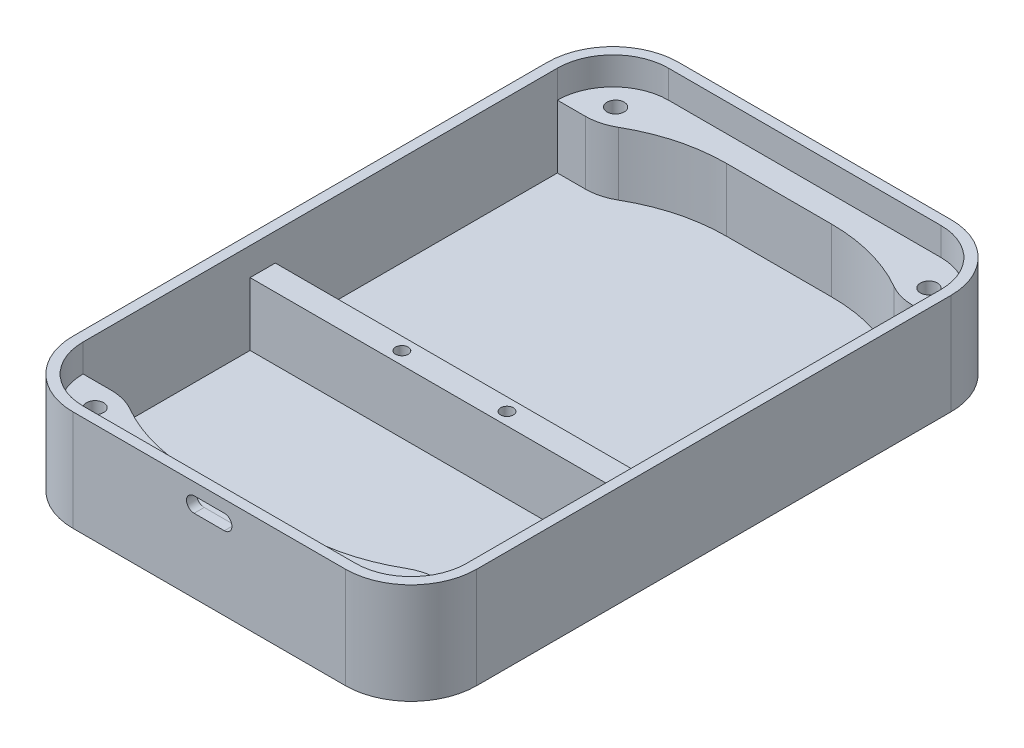
SolidWorks part; units mm, degrees
ref_plane "Alzado" through (0, 0, 0) normal (0, 0, 1) x (1, 0, 0)
ref_plane "Planta" through (0, 0, 0) normal (0, 1, 0) x (1, 0, 0)
ref_plane "Vista lateral" through (0, 0, 0) normal (1, 0, 0) x (0, 0, -1)
sketch "Croquis1" plane through (0, 0, 0) normal (0, 1, 0) x (1, 0, 0)
  line L0 (0, -55.2281) -> (0, 64.3245) construction
  line L1 (-27, 60) -> (27, 60)
  line L2 (-27, -60) -> (27, -60)
  line L3 (40, 47) -> (40, -47)
  line L5 (-40, 47) -> (-40, -47)
  line L6 (40, 47) -> (-40, -47) construction
  line L7 (40, -47) -> (-40, 47) construction
  arc A0 (27, 60) -> (40, 47) centre (27, 47) cw
  arc A1 (-27, 60) -> (-40, 47) centre (-27, 47) ccw
  arc A2 (-40, -47) -> (-27, -60) centre (-27, -47) ccw
  arc A3 (27, -60) -> (40, -47) centre (27, -47) ccw
  point P1 (0, 0)
  point P17 (0, 60)
  dimension "D2" = 80
  dimension "D3" = 13
  dimension "D1" = 120
extrude "Saliente-Extruir1" add sketch "Croquis1" along normal blind 20
shell "Vaciado1" thickness 2 removed face at (0, 20, 0)
sketch "Croquis2" plane through (0, 2, 0) normal (0, 1, 0) x (1, 0, 0)
  line L0 (0, 0) -> (0, -20.3372) construction
  line L1 (10.415, -33.255) -> (-10.415, -33.255) construction
  line L2 (10.415, -11.41) -> (-10.415, -11.41) construction
  line L3 (10.415, -11.41) -> (10.415, -55.1) construction
  line L4 (10.415, -55.1) -> (-10.415, -55.1) construction
  line L5 (-10.415, -11.41) -> (-10.415, -55.1) construction
  line L6 (-38, 47) -> (-38, -47) construction
  line L7 (38, -47) -> (38, 47) construction
  line L8 (-27, -58) -> (27, -58) construction
  line L9 (0, -47) -> (-10.415, -47) construction
  line L10 (-27, -58) -> (27, -58)
  line L11 (0, -47) -> (10.415, -47) construction
  line L12 (38, -8.91) -> (38, -13.91)
  line L13 (38, -13.91) -> (-38, -13.91)
  line L14 (38, -8.91) -> (-38, -8.91)
  line L15 (-38, -8.91) -> (-38, -13.91)
  line L16 (-38, 0) -> (38, 0) construction
  line L17 (-38, 47) -> (-38, -47) construction
  line L18 (38, -47) -> (38, 47) construction
  line L19 (-10.415, 47) -> (-32.4711, 47) construction
  line L20 (10.415, 47) -> (32.4711, 47) construction
  line L21 (0, 47) -> (10.415, 47) construction
  line L22 (-10.415, -52.9) -> (10.415, -52.9)
  line L23 (-32.4711, -47) -> (-38, -47)
  line L24 (32.4711, -47) -> (38, -47)
  line L25 (10.415, -47) -> (32.4711, -47) construction
  line L26 (-10.415, -47) -> (-32.4711, -47) construction
  line L27 (0, 47) -> (-10.415, 47) construction
  line L29 (32.4711, 47) -> (38, 47)
  line L30 (-32.4711, 47) -> (-38, 47)
  line L31 (-10.415, 52.9) -> (10.415, 52.9)
  line L32 (-27, 58) -> (27, 58)
  circle A0 centre (-10.415, -55.1) radius 1.25
  circle A1 centre (10.415, -55.1) radius 1.25
  circle A2 centre (-10.415, -11.41) radius 1.25
  circle A3 centre (10.415, -11.41) radius 1.25
  arc A4 (-38, -47) -> (-27, -58) centre (-27, -47) ccw construction
  arc A5 (-38, -47) -> (-27, -58) centre (-27, -47) ccw
  arc A6 (27, -58) -> (38, -47) centre (27, -47) ccw construction
  arc A7 (-38, -47) -> (-27, -58) centre (-27, -47) ccw construction
  arc A8 (27, -58) -> (38, -47) centre (27, -47) ccw
  arc A9 (-10.415, 52.9) -> (-27.319, 48.3782) centre (-10.415, 19.0428) ccw
  arc A10 (-27.319, 48.3782) -> (-32.4711, 47) centre (-32.4711, 57.3191) cw
  arc A11 (10.415, -52.9) -> (27.319, -48.3782) centre (10.415, -19.0428) ccw
  arc A12 (27.319, -48.3782) -> (32.4711, -47) centre (32.4711, -57.3191) cw
  arc A13 (-27.319, -48.3782) -> (-32.4711, -47) centre (-32.4711, -57.3191) ccw
  arc A14 (-10.415, -52.9) -> (-27.319, -48.3782) centre (-10.415, -19.0428) cw
  arc A15 (27.319, 48.3782) -> (32.4711, 47) centre (32.4711, 57.3191) ccw
  arc A16 (10.415, 52.9) -> (27.319, 48.3782) centre (10.415, 19.0428) cw
  arc A17 (27, 58) -> (38, 47) centre (27, 47) cw
  arc A18 (-38, 47) -> (-27, 58) centre (-27, 47) cw
  point P1 (0, 0)
  point P2 (0, -55.1)
  point P11 (0, -33.255)
  point P86 (0, 55.1)
  dimension "D5" = 2.5
  dimension "D8" = 33.8572
  dimension "D9" = 10.3191
  dimension "D1" = 43.69
  dimension "D2" = 20.83
  dimension "D3" = 2.5
  dimension "D4" = 5
  dimension "D6" = 2.9
  dimension "D7" = 5.1
extrude "Saliente-Extruir2" add sketch "Croquis2" along normal blind 12.5
sketch "Croquis3" plane through (0, 0, 60) normal (0, 0, 1) x (1, 0, 0)
  line L0 (0, 0) -> (0, 20) construction
  line L1 (-27, 20) -> (27, 20) construction
  line L2 (-3, 14.6) -> (3, 14.6)
  line L3 (-27, 0) -> (27, 0) construction
  line L4 (-3, 17.6) -> (3, 17.6)
  arc A0 (-3, 17.6) -> (-3, 14.6) centre (-3, 16.1) ccw
  arc A1 (3, 17.6) -> (3, 14.6) centre (3, 16.1) cw
  point P11 (0, 14.6)
  point P12 (0, 17.6)
  point P15 (-4.5, 16.1)
  point P16 (-4.5, 16.1)
  point P17 (4.5, 16.1)
  point P18 (4.5, 16.1)
  dimension "D2" = 9
  dimension "D1" = 14.6
  dimension "D3" = 3
extrude "Cortar-Extruir1" cut sketch "Croquis3" against normal up to next
sketch "Croquis4" plane through (0, 14.5, 0) normal (0, 1, 0) x (1, 0, 0)
  line L0 (-27, 58) -> (-27.319, 48.3782) construction
  line L1 (-27.319, 48.3782) -> (-34.7782, 54.7782) construction
  line L2 (0, 0) -> (0, 58) construction
  line L3 (27, 58) -> (-27, 58) construction
  line L4 (0, 0) -> (-38, 0) construction
  line L5 (-38, 47) -> (-38, -47) construction
  arc A0 (-27, 58) -> (-38, 47) centre (-27, 47) ccw construction
  arc A1 (-34.7782, 54.7782) -> (-27, 58) centre (-27, 47) cw construction
  circle A2 centre (-31.0486, 51.5782) radius 1.7
  circle A3 centre (31.0486, 51.5782) radius 1.7
  circle A4 centre (31.0486, -51.5782) radius 1.7
  circle A5 centre (-31.0486, -51.5782) radius 1.7
  point P9 (-34.7782, 54.7782)
  dimension "D1" = 3.4
extrude "Cortar-Extruir2" cut sketch "Croquis4" against normal up to next
sketch "Croquis5" plane through (0, 0, 0) normal (0, -1, 0) x (1, 0, 0)
  line L0 (0, -51.5782) -> (0, 51.5782) construction
  line L1 (-31.0486, 51.5782) -> (31.0486, 51.5782) construction
  line L2 (-31.0486, 51.5782) -> (-31.0486, -51.5782) construction
  line L3 (-31.0486, -51.5782) -> (31.0486, -51.5782) construction
  line L4 (31.0486, 51.5782) -> (31.0486, -51.5782) construction
  line L5 (-34.0986, 53.3391) -> (-34.0986, 49.8173)
  line L6 (-34.0986, 49.8173) -> (-31.0486, 48.0563)
  line L7 (-31.0486, 48.0563) -> (-27.9986, 49.8173)
  line L8 (-27.9986, 49.8173) -> (-27.9986, 53.3391)
  line L9 (-27.9986, 53.3391) -> (-31.0486, 55.1)
  line L10 (-31.0486, 55.1) -> (-34.0986, 53.3391)
  line L11 (31.0486, 0) -> (-31.0486, 0) construction
  line L12 (31.0486, 55.1) -> (34.0986, 53.3391)
  line L13 (27.9986, 53.3391) -> (31.0486, 55.1)
  line L14 (27.9986, 49.8173) -> (27.9986, 53.3391)
  line L15 (31.0486, 48.0563) -> (27.9986, 49.8173)
  line L16 (34.0986, 49.8173) -> (31.0486, 48.0563)
  line L17 (34.0986, 53.3391) -> (34.0986, 49.8173)
  line L18 (34.0986, -53.3391) -> (34.0986, -49.8173)
  line L19 (34.0986, -49.8173) -> (31.0486, -48.0563)
  line L20 (31.0486, -48.0563) -> (27.9986, -49.8173)
  line L21 (27.9986, -49.8173) -> (27.9986, -53.3391)
  line L22 (27.9986, -53.3391) -> (31.0486, -55.1)
  line L23 (31.0486, -55.1) -> (34.0986, -53.3391)
  line L24 (-31.0486, -55.1) -> (-34.0986, -53.3391)
  line L25 (-27.9986, -53.3391) -> (-31.0486, -55.1)
  line L26 (-27.9986, -49.8173) -> (-27.9986, -53.3391)
  line L27 (-31.0486, -48.0563) -> (-27.9986, -49.8173)
  line L28 (-34.0986, -49.8173) -> (-31.0486, -48.0563)
  line L29 (-34.0986, -53.3391) -> (-34.0986, -49.8173)
  circle A0 centre (-31.0486, 51.5782) radius 3.05 construction
  circle A1 centre (31.0486, 51.5782) radius 3.05 construction
  circle A2 centre (31.0486, -51.5782) radius 3.05 construction
  circle A3 centre (-31.0486, -51.5782) radius 3.05 construction
  dimension "D1" = 6.1
extrude "Cortar-Extruir3" cut sketch "Croquis5" against normal blind 4
